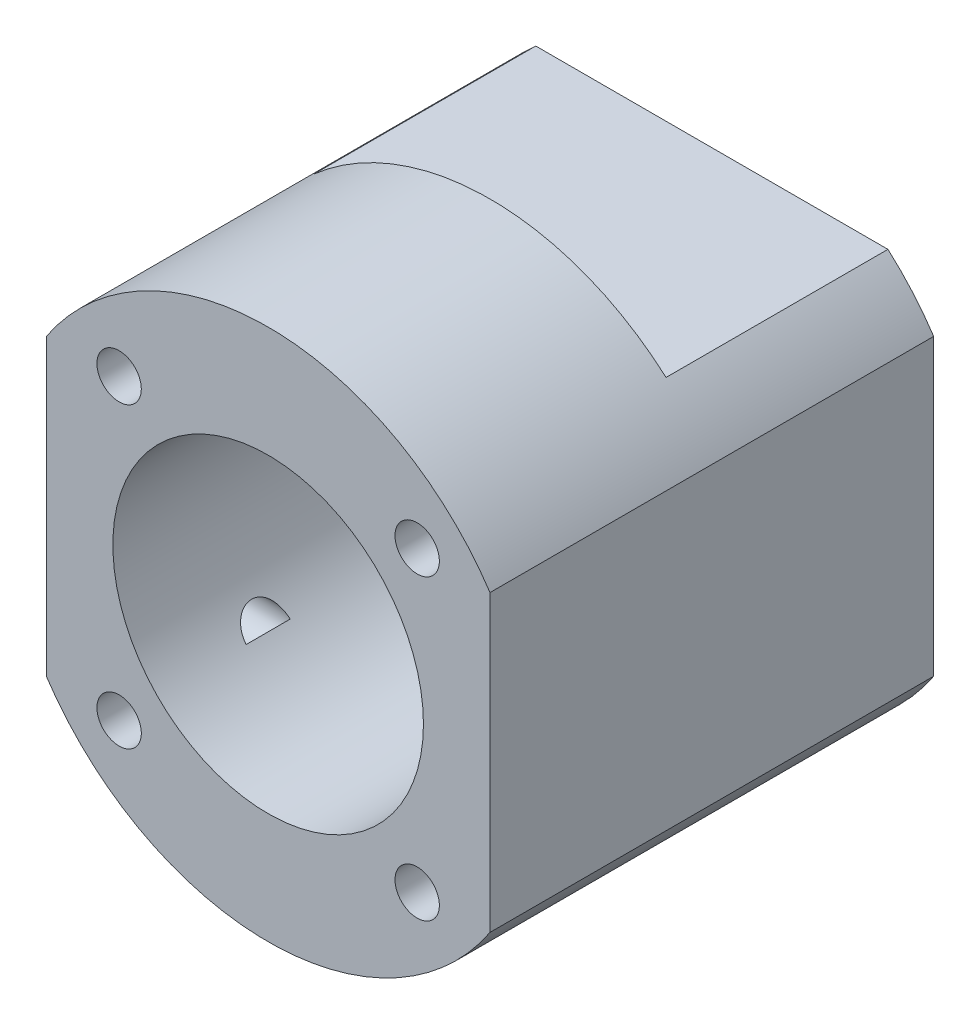
SolidWorks part; units mm, degrees
ref_plane "Piano frontale" through (0, 0, 0) normal (0, 0, 1) x (1, 0, 0)
ref_plane "Piano superiore" through (0, 0, 0) normal (0, 1, 0) x (1, 0, 0)
ref_plane "Piano destro" through (0, 0, 0) normal (1, 0, 0) x (0, 0, -1)
sketch "Schizzo1" plane through (0, 0, 0) normal (0, 0, 1) x (1, 0, 0)
  line L0 (0, 0) -> (-33.4653, 33.4653) construction
  line L1 (0, 0) -> (-48.3841, 0) construction
  line L2 (20, -13.2665) -> (20, 13.2665)
  line L3 (0, 0) -> (0, 37.5637) construction
  line L4 (-20, -13.2665) -> (-20, 13.2665)
  line L5 (20, -37.5637) -> (-20, 37.5637) construction
  line L6 (20, 37.5637) -> (-20, -37.5637) construction
  arc A0 (-20, -13.2665) -> (20, -13.2665) centre (0, 0) ccw
  arc A1 (20, 13.2665) -> (-20, 13.2665) centre (0, 0) ccw
  circle A2 centre (0, 0) radius 14
  dimension "D1" = 48
  dimension "D3" = 28
  dimension "D2" = 40
  dimension "D4" = 45
extrude "Estrusione-Estrusione1" add sketch "Schizzo1" against normal blind 40
sketch "Schizzo4" plane through (-20, 0, 0) normal (-1, 0, 0) x (0, 0, 1)
  line L0 (0, 0) -> (-40, 0) construction
  line L1 (0, 13.2665) -> (0, -13.2665) construction
  line L2 (-40, 13.2665) -> (-40, -13.2665) construction
  line L3 (-20, 13.2665) -> (-20, -13.2665) construction
  line L4 (-40, 13.2665) -> (0, 13.2665) construction
  line L5 (-40, -13.2665) -> (0, -13.2665) construction
  circle A0 centre (-10, 10) radius 2
  circle A1 centre (-10, -10) radius 2
  circle A2 centre (-30, -10) radius 2
  circle A3 centre (-30, 10) radius 2
  dimension "D3" = 4
  dimension "D1" = 10
  dimension "D2" = 10
extrude "Taglio-Estrusione1" cut sketch "Schizzo4" against normal blind 10
sketch "Schizzo5" plane through (0, 0, 0) normal (0, 0, 1) x (1, 0, 0)
  line L0 (0, 0) -> (0, 24) construction
  line L1 (0, 0) -> (-16.9706, 16.9706) construction
  line L2 (0, 0) -> (-20, 0) construction
  line L3 (-20, 13.2665) -> (-20, -13.2665) construction
  arc A0 (20, 13.2665) -> (-20, 13.2665) centre (0, 0) ccw construction
  circle A1 centre (0, 0) radius 19 construction
  circle A2 centre (-13.435, 13.435) radius 2
  circle A3 centre (13.435, 13.435) radius 2
  circle A4 centre (13.435, -13.435) radius 2
  circle A5 centre (-13.435, -13.435) radius 2
  point P11 (-13.435, 13.435)
  dimension "D2" = 38
  dimension "D3" = 4
  dimension "D1" = 45
extrude "Taglio-Estrusione2" cut sketch "Schizzo5" against normal blind 10
sketch "Schizzo6" plane through (0, 0, -40) normal (0, 0, -1) x (-1, 0, 0)
  line L0 (0, 0) -> (20, 0) construction
  line L1 (-15.8745, 18) -> (16.1288, 18)
  line L2 (-15.8745, 18) -> (-15.8745, 25.881)
  line L3 (-15.8745, 25.881) -> (16.1288, 25.881)
  line L4 (16.1288, 18) -> (16.1288, 25.881)
  line L5 (20, 13.2665) -> (20, -13.2665) construction
  line L6 (16.1288, -18) -> (16.1288, -25.881)
  line L7 (-15.8745, -25.881) -> (16.1288, -25.881)
  line L8 (-15.8745, -18) -> (-15.8745, -25.881)
  line L9 (-15.8745, -18) -> (16.1288, -18)
  arc A0 (20, 13.2665) -> (-20, 13.2665) centre (0, 0) ccw construction
  dimension "D1" = 18
extrude "Taglio-Estrusione3" cut sketch "Schizzo6" against normal blind 20
sketch "Sketch1" plane through (-20, 0, 0) normal (-1, 0, 0) x (0, 0, 1)
  line L0 (-20, 13.2665) -> (-20, -13.2665) construction
  line L1 (-40, 13.2665) -> (0, 13.2665) construction
  line L2 (-40, -13.2665) -> (0, -13.2665) construction
ref_plane "Plane1" through (0, 0, -20) normal (0, 0, 1) x (1, 0, 0)
